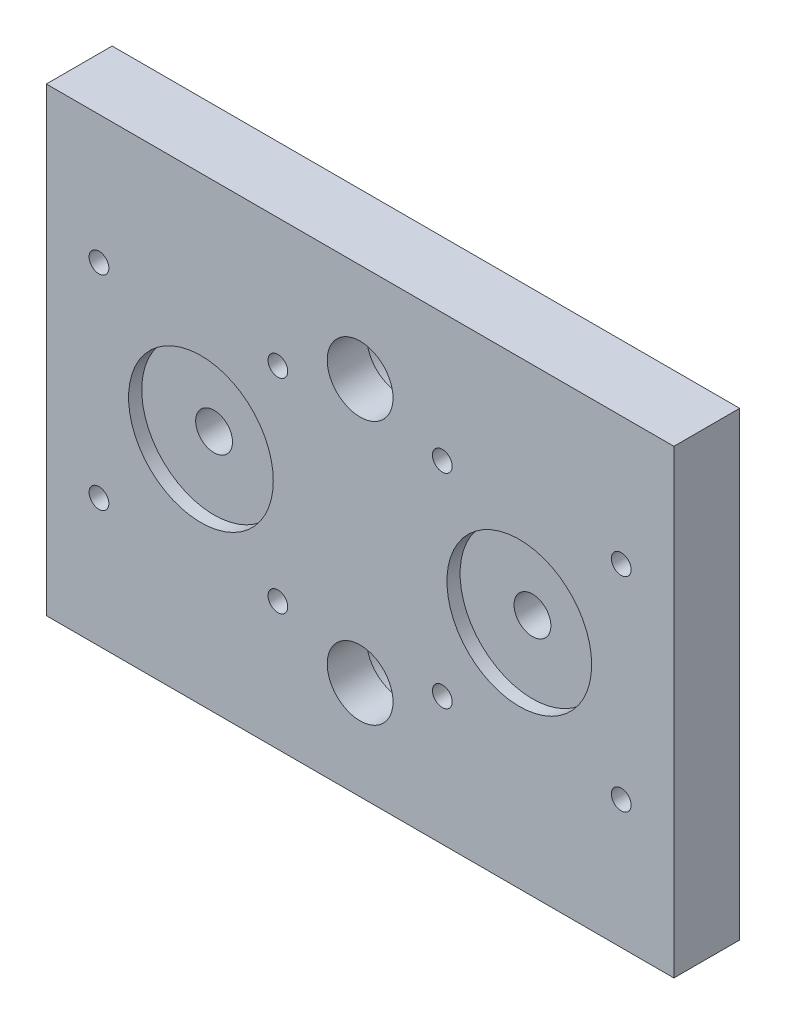
SolidWorks part; units mm, degrees
ref_plane "Front Plane" through (0, 0, 0) normal (0, 0, 1) x (1, 0, 0)
ref_plane "Top Plane" through (0, 0, 0) normal (0, 1, 0) x (1, 0, 0)
ref_plane "Right Plane" through (0, 0, 0) normal (1, 0, 0) x (0, 0, -1)
sketch "Sketch1" plane through (0, 0, 0) normal (0, 0, 1) x (1, 0, 0)
  line L0 (0, 0) -> (0, 40) construction
  line L2 (12.5, -15) -> (-12.5, -15)
  line L3 (12.5, -15) -> (12.5, 55)
  line L4 (12.5, 55) -> (-12.5, 55)
  line L5 (-12.5, -15) -> (-12.5, 55)
  line L6 (12.5, -15) -> (-12.5, 55) construction
  line L7 (12.5, 55) -> (-12.5, -15) construction
  circle A0 centre (0, 40) radius 7.9375
  circle A1 centre (0, 0) radius 7.9375
  point P5 (0, 20)
  dimension "D2" = 15.875
  dimension "D1" = 40
  dimension "D3" = 70
  dimension "D4" = 25
extrude "Boss-Extrude1" add sketch "Sketch1" along normal blind 10
sketch "Sketch2" plane through (0, 0, 10) normal (0, 0, 1) x (1, 0, 0)
  line L0 (12.5, 55) -> (-12.5, 55) construction
  line L1 (-47.7, 55) -> (-8.2, 55)
  line L3 (-47.7, -15) -> (-8.2, -15)
  line L4 (-8.2, 55) -> (-8.2, 36.9142)
  line L5 (-39.7, 35.5) -> (-8.7, 4.5) construction
  line L6 (-39.7, 4.5) -> (-8.7, 35.5) construction
  line L7 (-12.5, -15) -> (12.5, -15) construction
  line L8 (-8.2, 34.0858) -> (-8.2, 5.9142)
  line L9 (0, 55) -> (0, -15) construction
  line L10 (-8.7, 4.5) -> (-39.7, 4.5) construction
  line L11 (-8.7, 4.5) -> (-8.7, 35.5) construction
  line L12 (-8.7, 35.5) -> (-39.7, 35.5) construction
  line L13 (-39.7, 4.5) -> (-39.7, 35.5) construction
  line L14 (-8.7, 4.5) -> (-39.7, 35.5) construction
  line L15 (-8.7, 35.5) -> (-39.7, 4.5) construction
  line L16 (8.7, 35.5) -> (39.7, 4.5) construction
  line L17 (8.7, 4.5) -> (39.7, 35.5) construction
  line L18 (39.7, 4.5) -> (39.7, 35.5) construction
  line L19 (8.7, 35.5) -> (39.7, 35.5) construction
  line L20 (8.7, 4.5) -> (8.7, 35.5) construction
  line L21 (8.7, 4.5) -> (39.7, 4.5) construction
  line L22 (39.7, 4.5) -> (8.7, 35.5) construction
  line L23 (39.7, 35.5) -> (8.7, 4.5) construction
  line L24 (8.2, 55) -> (8.2, 36.9142)
  line L25 (47.7, -15) -> (8.2, -15)
  line L27 (47.7, 55) -> (8.2, 55)
  line L28 (-47.7, 55) -> (-47.7, -15)
  line L29 (47.7, 55) -> (47.7, -15)
  line L31 (-8.2, 3.0858) -> (-8.2, -15)
  line L32 (8.2, 3.0858) -> (8.2, -15)
  line L33 (8.2, 34.0858) -> (8.2, 5.9142)
  circle A0 centre (-39.7, 35.5) radius 1.5
  arc A1 (-8.2, 36.9142) -> (-8.2, 34.0858) centre (-8.7, 35.5) ccw
  arc A2 (-8.2, 5.9142) -> (-8.2, 3.0858) centre (-8.7, 4.5) ccw
  circle A3 centre (-39.7, 4.5) radius 1.5
  circle A4 centre (39.7, 4.5) radius 1.5
  arc A5 (8.2, 5.9142) -> (8.2, 3.0858) centre (8.7, 4.5) cw
  arc A6 (8.2, 36.9142) -> (8.2, 34.0858) centre (8.7, 35.5) cw
  circle A7 centre (39.7, 35.5) radius 1.5
  circle A8 centre (-24.2, 20) radius 2.8
  circle A9 centre (24.2, 20) radius 2.8
  point P0 (-24.2, 20)
  point P11 (-24.2, 20)
  point P34 (24.2, 20)
  dimension "D2" = 3
  dimension "D3" = 5.6
  dimension "D1" = 31
  dimension "D4" = 0.5
  dimension "D5" = 8
  dimension "D6" = 8.2
extrude "Boss-Extrude2" add sketch "Sketch2" against normal up to surface (10 mm away) up to face at (0, 20, 0)
sketch "Sketch6" plane through (0, 0, 10) normal (0, 0, 1) x (1, 0, 0)
  circle A0 centre (-12.5, 35.5) radius 1.5
  circle A1 centre (12.5, 35.5) radius 1.5
  circle A2 centre (-12.5, 4.5) radius 1.5
  circle A3 centre (12.5, 4.5) radius 1.5
  circle A5 centre (-39.7, 35.5) radius 1.5 construction
extrude "Cut-Extrude3" cut sketch "Sketch6" against normal up to surface (10 mm away) up to face at (0, 20, 0)
sketch "Sketch3" plane through (0, 0, 10) normal (0, 0, 1) x (1, 0, 0)
  circle A0 centre (0, 40) radius 7.9375
  circle A1 centre (0, 0) radius 7.9375
  circle A2 centre (0, 40) radius 7.9375 construction
  circle A3 centre (0, 40) radius 5
  circle A4 centre (0, 0) radius 5
  circle A8 centre (0, 0) radius 7.9375 construction
  dimension "D1" = 10
extrude "Boss-Extrude3" add sketch "Sketch3" against normal blind 6.0216
sketch "Sketch4" plane through (0, 0, 10) normal (0, 0, 1) x (1, 0, 0)
  circle A0 centre (-24.2, 20) radius 11
  circle A1 centre (24.2, 20) radius 11
  dimension "D1" = 22
extrude "Cut-Extrude1" cut sketch "Sketch4" against normal blind 2
sketch "Sketch5" plane through (0, 0, 0) normal (0, 0, -1) x (-1, 0, 0)
  circle A0 centre (-39.7, 35.5) radius 2.75
  circle A1 centre (-12.5, 35.5) radius 2.75
  circle A2 centre (-39.7, 4.5) radius 2.75
  circle A3 centre (-12.5, 4.5) radius 2.75
  circle A4 centre (12.5, 35.5) radius 2.75
  circle A5 centre (39.7, 35.5) radius 2.75
  circle A6 centre (12.5, 4.5) radius 2.75
  circle A7 centre (39.7, 4.5) radius 2.75
  circle A9 centre (12.5, 4.5) radius 1.5 construction
  circle A10 centre (-12.5, 4.5) radius 1.5 construction
  circle A11 centre (-12.5, 35.5) radius 1.5 construction
  circle A12 centre (12.5, 35.5) radius 1.5 construction
  dimension "D1" = 5.5
extrude "Cut-Extrude2" cut sketch "Sketch5" against normal blind 3.1
sketch "Sketch11" plane through (0, 0, 0) normal (0, 0, -1) x (-1, 0, 0)
  circle A0 centre (-24.2, 20) radius 10.2
  circle A1 centre (24.2, 20) radius 10.2
  dimension "D1" = 20.4
extrude "Cut-Extrude6" cut sketch "Sketch11" against normal blind 2
sketch "Sketch12" plane through (0, 0, 0) normal (0, 0, -1) x (-1, 0, 0)
  circle A0 centre (24.2, 20) radius 12.5
  dimension "D1" = 25
extrude "Cut-Extrude8" cut sketch "Sketch12" against normal up to surface (2 mm away) up to face at (-34.4, 20, 2)
